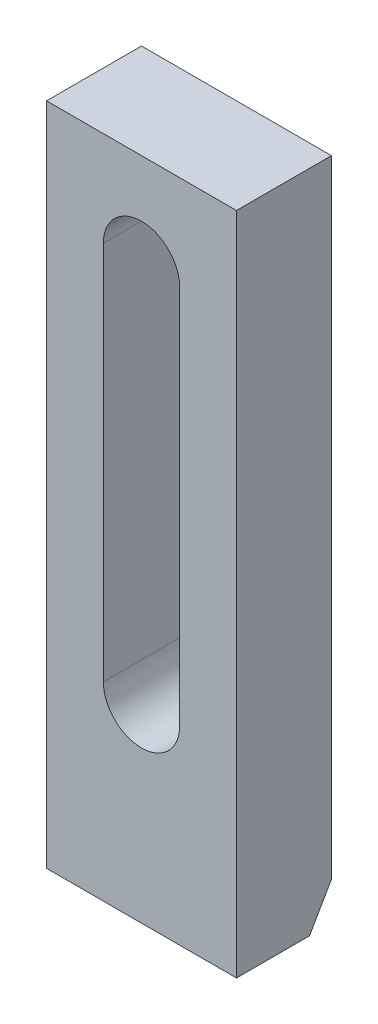
SolidWorks part; units mm, degrees
ref_plane "Спереди" through (0, 0, 0) normal (0, 0, 1) x (1, 0, 0)
ref_plane "Сверху" through (0, 0, 0) normal (0, 1, 0) x (1, 0, 0)
ref_plane "Справа" through (0, 0, 0) normal (1, 0, 0) x (0, 0, -1)
sketch "Эскиз1" plane through (0, 0, 0) normal (0, 0, 1) x (1, 0, 0)
  line L1 (0, 0) -> (50, 0)
  line L2 (0, 0) -> (0, 175)
  line L3 (0, 175) -> (50, 175)
  line L4 (50, 0) -> (50, 175)
  dimension "D1" = 50
  dimension "D2" = 175
extrude "Бобышка-Вытянуть1" add sketch "Эскиз1" along normal blind 25
sketch "Эскиз2" plane through (0, 0, 25) normal (0, 0, 1) x (1, 0, 0)
  line L1 (14.95, 50) -> (14.95, 150)
  line L2 (35.05, 50) -> (35.05, 150)
  line L3 (0, 175) -> (0, 0) construction
  line L4 (0, 0) -> (50, 0) construction
  arc A0 (14.95, 50) -> (35.05, 50) centre (25, 50) ccw
  arc A1 (14.95, 150) -> (35.05, 150) centre (25, 150) cw
  point P3 (0, 0)
  point P7 (14.95, 100)
  point P10 (35.05, 100)
  dimension "D1" = 25
  dimension "D2" = 50
extrude "Вырез-Вытянуть1" cut sketch "Эскиз2" against normal through all
chamfer "Фаска1" distance 10 angle 30 1 edges at (25, 0, 0) first distance on face at (25, 100, 0)
